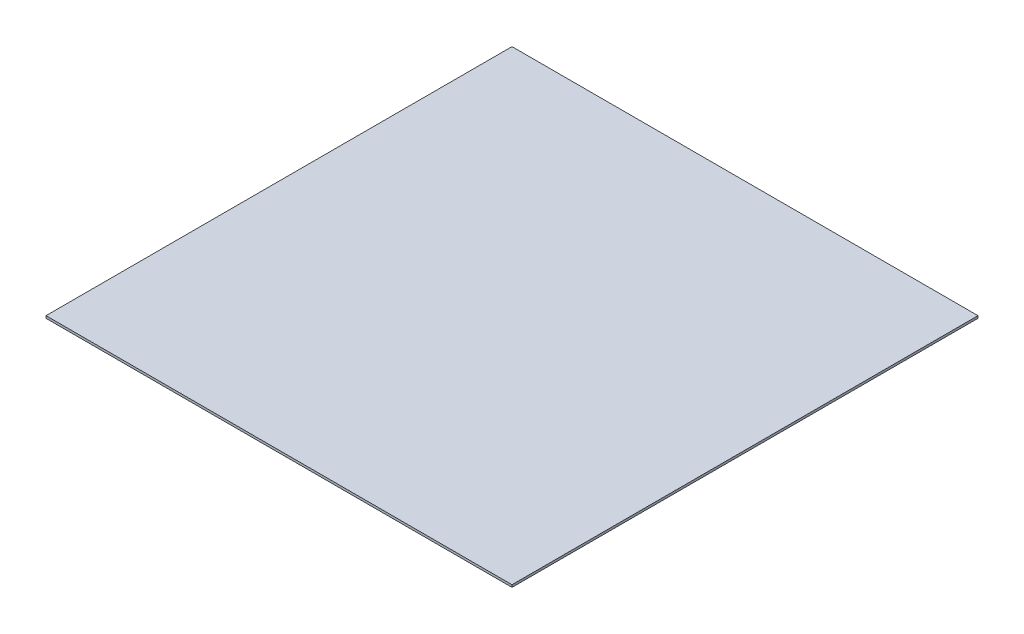
SolidWorks part; units mm, degrees
material "Ouro puro"
ref_plane "Plano frontal" through (0, 0, 0) normal (0, 0, 1) x (1, 0, 0)
ref_plane "Plano superior" through (0, 0, 0) normal (0, 1, 0) x (1, 0, 0)
ref_plane "Plano direito" through (0, 0, 0) normal (1, 0, 0) x (0, 0, -1)
sketch "Esboço1" plane through (0, 0, 0) normal (0, 1, 0) x (1, 0, 0)
  line L1 (0, 0) -> (1000, 0)
  line L2 (0, 0) -> (0, 1000)
  line L3 (0, 1000) -> (1000, 1000)
  line L4 (1000, 0) -> (1000, 1000)
  dimension "D1" = 1000
  dimension "D2" = 1000
extrude "Ressalto-extrusão1" add sketch "Esboço1" along normal blind 5
